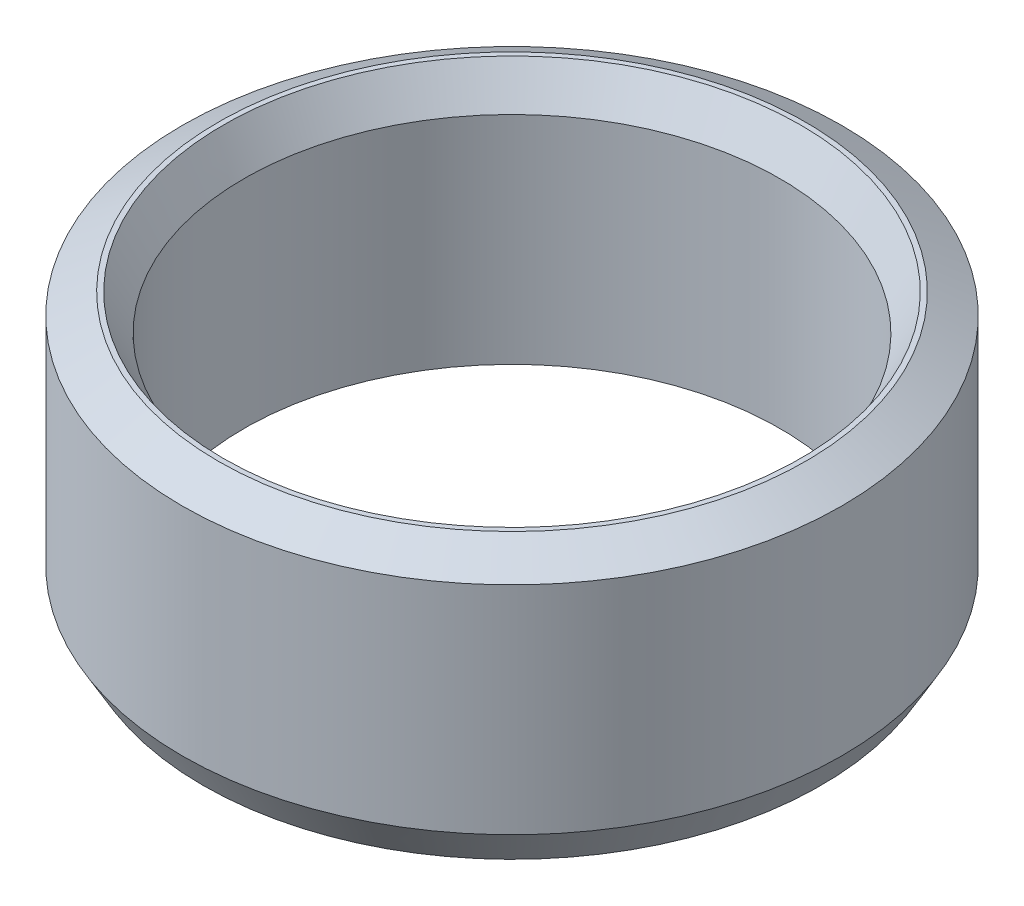
SolidWorks part; units mm, degrees
ref_plane "Front Plane" through (0, 0, 0) normal (0, 0, 1) x (1, 0, 0)
ref_plane "Top Plane" through (0, 0, 0) normal (0, 1, 0) x (1, 0, 0)
ref_plane "Right Plane" through (0, 0, 0) normal (1, 0, 0) x (0, 0, -1)
sketch "Sketch1" plane through (0, 0, 0) normal (0, 1, 0) x (1, 0, 0)
  circle A0 centre (0, 0) radius 27.5
  dimension "SLEEVE_OD" = 55
extrude "Boss-Extrude1" add sketch "Sketch1" along normal blind 22.7844
sketch "Sketch2" plane through (0, 0, 0) normal (0, 1, 0) x (1, 0, 0)
  circle A0 centre (0, 0) radius 22.3495
  dimension "BORE_D" = 44.699
extrude "Cut-Extrude1" cut sketch "Sketch2" along normal through all
chamfer "Chamfer1" distance 1.7325 angle 60 4 edges at (0, 22.7844, 22.3495) (0, 0, 22.3495) (0, 0, 27.5) (0, 22.7844, 27.5) first distance on face at (0, 22.7844, 22.3495) first distance on face at (0, 0, 22.3495) first distance on face at (0, 22.7844, 27.5)
